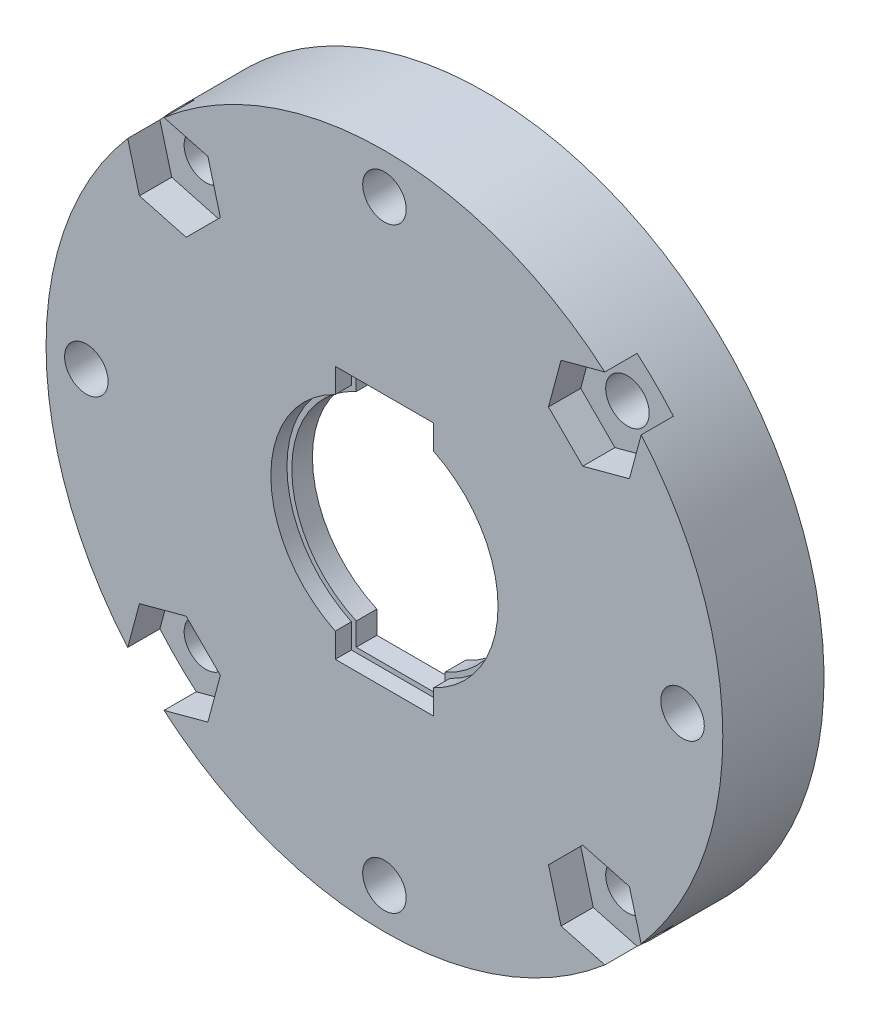
SolidWorks part; units mm, degrees
ref_plane "Front Plane" through (0, 0, 0) normal (0, 0, 1) x (1, 0, 0)
ref_plane "Top Plane" through (0, 0, 0) normal (0, 1, 0) x (1, 0, 0)
ref_plane "Right Plane" through (0, 0, 0) normal (1, 0, 0) x (0, 0, -1)
ref_axis "Z" through (0, 0, -0.1) along (0, 0, 1)
sketch "Sketch3" plane through (0, 0, 0) normal (0, 0, 1) x (1, 0, 0)
  line L132 (3.05, 6.3548) -> (3.05, 6.3561) construction
  line L133 (-3.05, 6.3561) -> (-3.05, 6.3548) construction
  line L134 (3.05, -6.3561) -> (3.05, -6.355) construction
  line L135 (-3.05, -6.355) -> (-3.05, -6.3561) construction
  line L198 (3.05, 6.3548) -> (3.05, 7.8744)
  line L199 (3.05, 7.8744) -> (-3.05, 7.8744)
  line L200 (-3.05, 7.8744) -> (-3.05, 6.3548)
  line L201 (-3.05, 6.3548) -> (-3.4914, 6.1247)
  line L202 (-3.4914, 6.1247) -> (-3.9416, 5.8451)
  line L203 (-3.9416, 5.8451) -> (-4.3696, 5.5325)
  line L204 (-4.3696, 5.5325) -> (-4.7729, 5.1886)
  line L205 (-4.7729, 5.1886) -> (-5.1492, 4.8154)
  line L206 (-5.1492, 4.8154) -> (-5.4964, 4.4149)
  line L207 (-5.4964, 4.4149) -> (-5.8125, 3.9896)
  line L208 (-5.8125, 3.9896) -> (-6.0958, 3.5417)
  line L209 (-6.0958, 3.5417) -> (-6.3446, 3.0737)
  line L210 (-6.3446, 3.0737) -> (-6.5576, 2.5884)
  line L211 (-6.5576, 2.5884) -> (-6.7335, 2.0885)
  line L212 (-6.7335, 2.0885) -> (-6.8714, 1.5768)
  line L213 (-6.8714, 1.5768) -> (-6.9705, 1.0561)
  line L214 (-6.9705, 1.0561) -> (-7.0301, 0.5295)
  line L215 (-7.0301, 0.5295) -> (-7.05, -0.0001)
  line L216 (-7.05, -0.0001) -> (-7.0301, -0.5297)
  line L217 (-7.0301, -0.5297) -> (-6.9705, -1.0563)
  line L218 (-6.9705, -1.0563) -> (-6.8714, -1.577)
  line L219 (-6.8714, -1.577) -> (-6.7335, -2.0887)
  line L220 (-6.7335, -2.0887) -> (-6.5576, -2.5887)
  line L221 (-6.5576, -2.5887) -> (-6.3446, -3.074)
  line L222 (-6.3446, -3.074) -> (-6.0958, -3.5419)
  line L223 (-6.0958, -3.5419) -> (-5.8125, -3.9898)
  line L224 (-5.8125, -3.9898) -> (-5.4964, -4.4152)
  line L225 (-5.4964, -4.4152) -> (-5.1492, -4.8156)
  line L226 (-5.1492, -4.8156) -> (-4.7729, -5.1888)
  line L227 (-4.7729, -5.1888) -> (-4.3696, -5.5327)
  line L228 (-4.3696, -5.5327) -> (-3.9416, -5.8453)
  line L229 (-3.9416, -5.8453) -> (-3.4914, -6.1249)
  line L230 (-3.4914, -6.1249) -> (-3.05, -6.355)
  line L231 (-3.05, -6.355) -> (-3.05, -7.8747)
  line L232 (-3.05, -7.8747) -> (3.05, -7.8747)
  line L233 (3.05, -7.8747) -> (3.05, -6.355)
  line L234 (3.05, -6.355) -> (3.4914, -6.1249)
  line L235 (3.4914, -6.1249) -> (3.9417, -5.8453)
  line L236 (3.9417, -5.8453) -> (4.3696, -5.5327)
  line L237 (4.3696, -5.5327) -> (4.7729, -5.1888)
  line L238 (4.7729, -5.1888) -> (5.1492, -4.8156)
  line L239 (5.1492, -4.8156) -> (5.4964, -4.4152)
  line L240 (5.4964, -4.4152) -> (5.8125, -3.9898)
  line L241 (5.8125, -3.9898) -> (6.0958, -3.5419)
  line L242 (6.0958, -3.5419) -> (6.3447, -3.074)
  line L243 (6.3447, -3.074) -> (6.5576, -2.5887)
  line L244 (6.5576, -2.5887) -> (6.7336, -2.0887)
  line L245 (6.7336, -2.0887) -> (6.8714, -1.577)
  line L246 (6.8714, -1.577) -> (6.9705, -1.0563)
  line L247 (6.9705, -1.0563) -> (7.0301, -0.5297)
  line L248 (7.0301, -0.5297) -> (7.05, -0.0001)
  line L249 (7.05, -0.0001) -> (7.0301, 0.5295)
  line L250 (7.0301, 0.5295) -> (6.9705, 1.0561)
  line L251 (6.9705, 1.0561) -> (6.8714, 1.5768)
  line L252 (6.8714, 1.5768) -> (6.7336, 2.0885)
  line L253 (6.7336, 2.0885) -> (6.5576, 2.5884)
  line L254 (6.5576, 2.5884) -> (6.3447, 3.0737)
  line L255 (6.3447, 3.0737) -> (6.0958, 3.5417)
  line L256 (6.0958, 3.5417) -> (5.8125, 3.9896)
  line L257 (5.8125, 3.9896) -> (5.4964, 4.4149)
  line L258 (5.4964, 4.4149) -> (5.1492, 4.8154)
  line L259 (5.1492, 4.8154) -> (4.7729, 5.1886)
  line L260 (4.7729, 5.1886) -> (4.3696, 5.5325)
  line L261 (4.3696, 5.5325) -> (3.9417, 5.8451)
  line L262 (3.9417, 5.8451) -> (3.4914, 6.1247)
  line L263 (3.4914, 6.1247) -> (3.05, 6.3548)
  line L264 (3.05, 6.3561) -> (3.05, 7.8744)
  line L265 (3.05, 7.8744) -> (-3.05, 7.8744)
  line L266 (-3.05, 7.8744) -> (-3.05, 6.3561)
  line L297 (-3.05, -6.3561) -> (-3.05, -7.8747)
  line L298 (-3.05, -7.8747) -> (3.05, -7.8747)
  line L299 (3.05, -7.8747) -> (3.05, -6.3561)
  arc A1 (-3.05, 6.3561) -> (-3.05, -6.3561) centre (0, 0) ccw
  arc A2 (3.05, 6.3561) -> (-3.05, 6.3561) centre (0, 0) ccw construction
  arc A3 (3.05, -6.3561) -> (3.05, 6.3561) centre (0, 0) ccw
  arc A4 (-3.05, -6.3561) -> (3.05, -6.3561) centre (0, 0) ccw construction
  circle A5 centre (0, 0) radius 21
  dimension "D1" = 14.1
  dimension "D3" = 42
  dimension "D2" = 0.05
extrude "Boss-Extrude2" add sketch "Sketch3" against normal blind 1
sketch "Sketch4" plane through (0, 0, -1) normal (0, 0, -1) x (-1, 0, 0)
  line L33 (2.75, 6.1644) -> (2.75, 7.5744)
  line L34 (2.75, 7.5744) -> (-2.75, 7.5744)
  line L35 (-2.75, 7.5744) -> (-2.75, 6.1644)
  line L36 (-2.75, -6.1644) -> (-2.75, -7.5747)
  line L37 (-2.75, -7.5747) -> (2.75, -7.5747)
  line L38 (2.75, -7.5747) -> (2.75, -6.1644)
  line L39 (2.75, 6.1644) -> (2.75, 7.5744)
  line L40 (2.75, 7.5744) -> (-2.75, 7.5744)
  line L41 (-2.75, 7.5744) -> (-2.75, 6.1644)
  line L42 (-2.75, -6.1644) -> (-2.75, -7.5747)
  line L43 (-2.75, -7.5747) -> (2.75, -7.5747)
  line L44 (2.75, -7.5747) -> (2.75, -6.1644)
  circle A13 centre (0, 0) radius 21 construction
  circle A14 centre (0, 0) radius 21
  arc A15 (-2.75, 6.1644) -> (-2.75, -6.1644) centre (0, 0) ccw
  arc A16 (2.75, -6.1644) -> (2.75, 6.1644) centre (0, 0) ccw
  arc A17 (-2.75, 6.1644) -> (-2.75, -6.1644) centre (0, 0) ccw
  arc A18 (2.75, -6.1644) -> (2.75, 6.1644) centre (0, 0) ccw
  dimension "D1" = 0.3
extrude "Boss-Extrude3" add sketch "Sketch4" along normal blind 5.28
sketch "Sketch5" plane through (0, 0, -6.28) normal (0, 0, -1) x (-1, 0, 0)
  circle A0 centre (0, 0) radius 16.5
  dimension "D1" = 33
extrude "Cut-Extrude1" cut sketch "Sketch5" against normal blind 4
sketch "Sketch6" plane through (0, 0, 0) normal (0, 0, 1) x (1, 0, 0)
  line L0 (0, 0) -> (13.0815, 13.0815) construction
  line L1 (-16.3801, 0) -> (0, 0) construction
  line L3 (13.8585, 15.9814) -> (10.9586, 15.2044)
  line L4 (10.9586, 15.2044) -> (10.1816, 12.3044)
  line L5 (10.1816, 12.3044) -> (12.3044, 10.1816)
  line L6 (12.3044, 10.1816) -> (15.2044, 10.9586)
  line L7 (15.2044, 10.9586) -> (15.9814, 13.8585)
  line L8 (15.9814, 13.8585) -> (13.8585, 15.9814)
  circle A0 centre (13.0815, 13.0815) radius 2.6 construction
  dimension "D3" = 5.2
  dimension "D1" = 135
  dimension "D2" = 18.5
extrude "Cut-Extrude2" cut sketch "Sketch6" against normal blind 2
sketch "Sketch8" plane through (0, 0, 0) normal (0, 0, 1) x (1, 0, 0)
  line L0 (36.6653, 0) -> (49.0214, 0) construction
  line L1 (0, 0) -> (13.0815, 13.0815) construction
  circle A0 centre (0, 0) radius 18.5 construction
  circle A1 centre (13.0815, 13.0815) radius 1.35
  dimension "D1" = 37
  dimension "D3" = 2.7
  dimension "D2" = 135
extrude "Cut-Extrude4" cut sketch "Sketch8" against normal through all
pattern_circular "CirPattern1" count 4 over 360 about axis through (0, 0, -0.1) along (0, 0, 1) of "Cut-Extrude2", "Cut-Extrude4"
ref_plane "Plane4" through (0, 0, 0) normal (-0.7071, 0.7071, 0) x (0, 0, 1)
pattern_circular "CirPattern2" count 8 over 360 about axis through (0, 0, -0.1) along (0, 0, 1) of "Cut-Extrude4"
